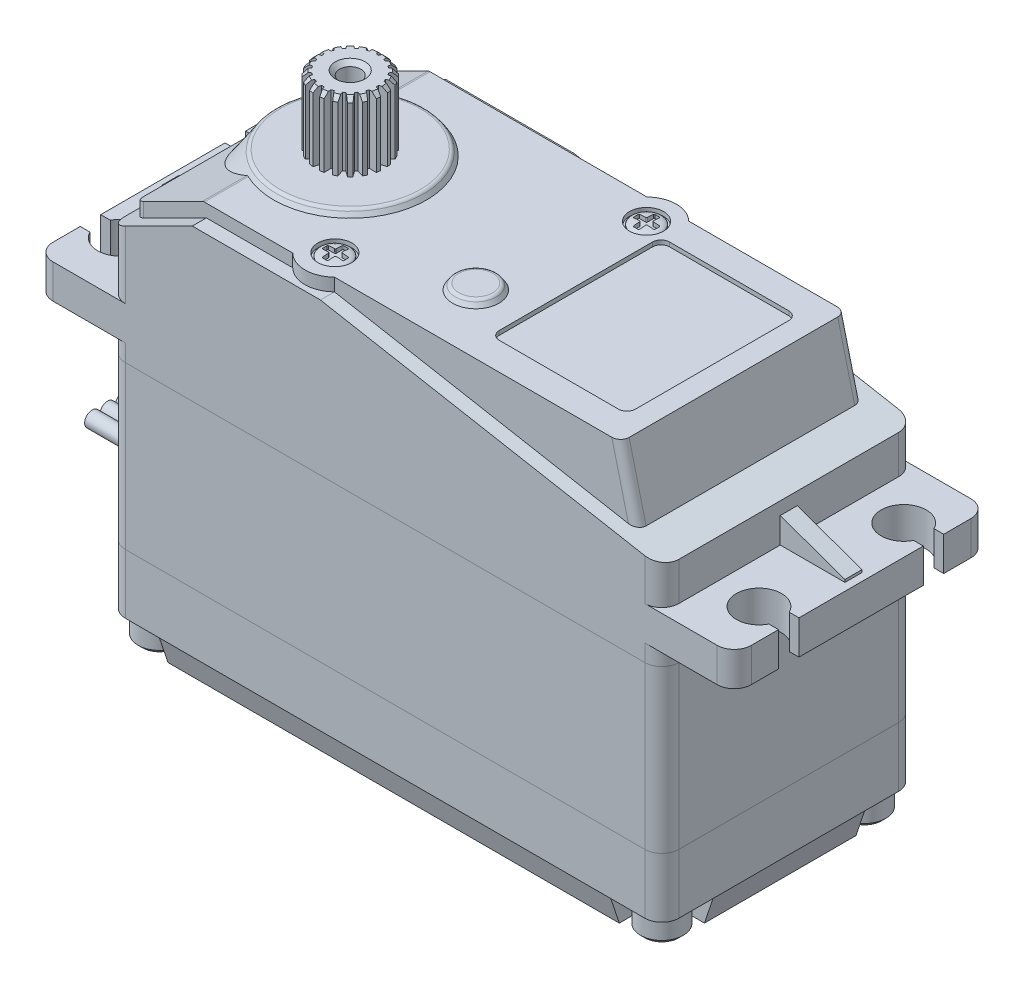
SolidWorks part; units mm, degrees
ref_plane "Front Plane" through (0, 0, 0) normal (0, 0, 1) x (1, 0, 0)
ref_plane "Top Plane" through (0, 0, 0) normal (0, 1, 0) x (1, 0, 0)
ref_plane "Right Plane" through (0, 0, 0) normal (1, 0, 0) x (0, 0, -1)
sketch "Sketch1" plane through (0, 0, 0) normal (0, 1, 0) x (1, 0, 0)
  line L0 (11.399, -13.25) -> (47, -13.25)
  line L1 (-12, 13.25) -> (21.601, 13.25)
  line L2 (-12, 13.25) -> (-12, -13.25)
  line L3 (-12, -13.25) -> (6.5, -13.25)
  line L4 (47, 13.25) -> (47, -13.25)
  line L5 (-12, 13.25) -> (47, -13.25) construction
  line L6 (-12, -13.25) -> (47, 13.25) construction
  line L7 (26.5, 13.25) -> (47, 13.25)
  arc A0 (6.5, -13.25) -> (11.399, -13.25) centre (8.9495, -10.75) ccw
  arc A1 (26.5, 13.25) -> (21.601, 13.25) centre (24.0505, 10.75) ccw
  point P0 (17.5, 0)
  dimension "D4" = 7
  dimension "D1" = 59
  dimension "D2" = 26.5
  dimension "D3" = 47
  dimension "D5" = 2.5
  dimension "D6" = 2.5
  dimension "D7" = 18.5
  dimension "D8" = 20.5
extrude "Boss-Extrude1" add sketch "Sketch1" against normal blind 8
chamfer "Chamfer1" distance 4 distance2 8 1 edges at (-12, 0, 0) first distance on face at (-12, -4, 0)
chamfer "Chamfer2" distance 8 distance2 2 1 edges at (47, 0, 0) first distance on face at (47, -4, 0)
fillet "Fillet1" radius 1 4 edges at (46, -4, -13.25) (46, -4, 13.25) (-12, -6, -13.25) (-12, -6, 13.25)
sketch "Sketch2" plane through (0, 0, 0) normal (0, 1, 0) x (1, 0, 0)
  line L0 (21, -8.5) -> (0, -8.5) construction
  circle A0 centre (0, 0) radius 8.5
  circle A1 centre (21, -6.25) radius 2.25
  dimension "D1" = 17
  dimension "D2" = 4.5
  dimension "D3" = 21
extrude "Boss-Extrude2" add sketch "Sketch2" against normal blind 5 draft 34 from offset 0.7 draft outward yes
fillet "Fillet2" radius 0.5 1 edges at (21, 0.7, 8.5)
sketch "Sketch3" plane through (0, 0, 0) normal (0, 0, 1) x (1, 0, 0)
  line L0 (-3.6459, -1.5) -> (-13.5, -6.4271)
  line L1 (-13.5, -6.4271) -> (-13.5, -13.3216)
  line L2 (-13.5, -13.3216) -> (-22, -13.3216)
  line L3 (-22, -13.3216) -> (-22, -17.3216)
  line L4 (-22, -17.3216) -> (-13.5, -17.3216)
  line L5 (-13.5, -17.3216) -> (-13.5, -19.3216)
  line L6 (-13.5, -19.3216) -> (51.5, -19.3216)
  line L7 (51.5, -19.3216) -> (51.5, -17.3216)
  line L8 (51.5, -17.3216) -> (60, -17.3216)
  line L9 (60, -17.3216) -> (60, -13.3216)
  line L10 (60, -13.3216) -> (51.5, -13.3216)
  line L11 (51.5, -13.3216) -> (51.5, -8.8216)
  line L12 (51.5, -8.8216) -> (11.399, -1.5)
  line L13 (11.399, -8) -> (11.399, 0) construction
  line L14 (11.399, -1.5) -> (-3.6459, -1.5)
  line L15 (-4, 0) -> (-11, -3.5) construction
  line L16 (-4, 0) -> (6.5, 0) construction
  line L17 (-12, -8) -> (-12, -4) construction
  dimension "D1" = 2
  dimension "D2" = 4
  dimension "D3" = 4.5
  dimension "D4" = 1.5
  dimension "D5" = 1.5
  dimension "D6" = 1.5
  dimension "D7" = 65
  dimension "D8" = 8.5
extrude "Boss-Extrude3" add sketch "Sketch3" along normal mid plane 29.8
fillet "Fillet3" radius 2 12 edges at (60, -15.3216, -14.9) (60, -15.3216, 14.9) (-22, -15.3216, 14.9) (-22, -15.3216, -14.9) (51.5, -18.3216, 14.9) (51.5, -18.3216, -14.9) (-13.5, -18.3216, 14.9) (-13.5, -18.3216, -14.9) (-13.5, -9.8743, -14.9) (-13.5, -9.8743, 14.9) (51.5, -11.0716, -14.9) (51.5, -11.0716, 14.9)
sketch "Sketch4" plane through (0, 0, 0) normal (0, 1, 0) x (1, 0, 0)
  line L0 (45, -12.25) -> (45, 12.25) construction
  line L1 (27.5, 10) -> (41.5, 10)
  line L2 (26.5, 9) -> (26.5, -9)
  line L3 (27.5, -10) -> (41.5, -10)
  line L4 (42.5, 9) -> (42.5, -9)
  line L5 (26.5, 10) -> (42.5, -10) construction
  line L6 (26.5, -10) -> (42.5, 10) construction
  circle A0 centre (24.0505, 10.75) radius 2
  circle A1 centre (8.9495, -10.75) radius 2
  arc A2 (41.5, 10) -> (42.5, 9) centre (41.5, 9) cw
  arc A3 (27.5, 10) -> (26.5, 9) centre (27.5, 9) ccw
  arc A4 (26.5, -9) -> (27.5, -10) centre (27.5, -9) ccw
  arc A5 (41.5, -10) -> (42.5, -9) centre (41.5, -9) ccw
  point P0 (34.5, 0)
  dimension "D1" = 4
  dimension "D5" = 1
  dimension "D2" = 20
  dimension "D3" = 16
  dimension "D4" = 2.5
extrude "Cut-Extrude1" cut sketch "Sketch4" against normal blind 0.5
sketch "Sketch5" plane through (0, -13.3216, 0) normal (0, 1, 0) x (1, 0, 0)
  line L0 (-22, 0) -> (60, 0) construction
  line L1 (-22, -12.9) -> (-22, 12.9) construction
  line L2 (60, -12.9) -> (60, 12.9) construction
  line L3 (19, 0) -> (19, 21.0756) construction
  line L4 (58.8627, -7.3) -> (60, -7.3)
  line L5 (58.8627, -9.7) -> (60, -9.7)
  line L6 (60, -9.7) -> (60, -7.3)
  line L7 (60, 9.7) -> (60, 7.3)
  line L8 (58.8627, 9.7) -> (60, 9.7)
  line L9 (58.8627, 7.3) -> (60, 7.3)
  line L10 (-20.8627, 7.3) -> (-22, 7.3)
  line L11 (-20.8627, 9.7) -> (-22, 9.7)
  line L12 (-22, 9.7) -> (-22, 7.3)
  line L13 (-22, -9.7) -> (-22, -7.3)
  line L14 (-20.8627, -9.7) -> (-22, -9.7)
  line L15 (-20.8627, -7.3) -> (-22, -7.3)
  arc A0 (58.8627, -7.3) -> (58.8627, -9.7) centre (56.5, -8.5) ccw
  arc A1 (58.8627, 7.3) -> (58.8627, 9.7) centre (56.5, 8.5) cw
  arc A2 (-20.8627, 7.3) -> (-20.8627, 9.7) centre (-18.5, 8.5) ccw
  arc A3 (-20.8627, -7.3) -> (-20.8627, -9.7) centre (-18.5, -8.5) cw
  dimension "D1" = 17
  dimension "D3" = 5.3
  dimension "D2" = 75
  dimension "D4" = 2.4
extrude "Cut-Extrude2" cut sketch "Sketch5" against normal through all
sketch "Sketch6" plane through (0, -19.3216, 0) normal (0, -1, 0) x (1, 0, 0)
  line L4 (51.5, -12.9) -> (51.5, 12.9)
  line L5 (49.5, 14.9) -> (-11.5, 14.9)
  line L6 (-13.5, 12.9) -> (-13.5, -12.9)
  line L7 (-11.5, -14.9) -> (49.5, -14.9)
  line L8 (51.5, -12.9) -> (51.5, 12.9)
  line L9 (49.5, 14.9) -> (-11.5, 14.9)
  line L10 (-13.5, 12.9) -> (-13.5, -12.9)
  line L11 (-11.5, -14.9) -> (49.5, -14.9)
  arc A4 (51.5, 12.9) -> (49.5, 14.9) centre (49.5, 12.9) ccw
  arc A5 (-11.5, 14.9) -> (-13.5, 12.9) centre (-11.5, 12.9) ccw
  arc A6 (-13.5, -12.9) -> (-11.5, -14.9) centre (-11.5, -12.9) ccw
  arc A7 (49.5, -14.9) -> (51.5, -12.9) centre (49.5, -12.9) ccw
  arc A8 (51.5, 12.9) -> (49.5, 14.9) centre (49.5, 12.9) ccw
  arc A9 (-11.5, 14.9) -> (-13.5, 12.9) centre (-11.5, 12.9) ccw
  arc A10 (-13.5, -12.9) -> (-11.5, -14.9) centre (-11.5, -12.9) ccw
  arc A11 (49.5, -14.9) -> (51.5, -12.9) centre (49.5, -12.9) ccw
  dimension "D1" = 0
extrude "Boss-Extrude4" add sketch "Sketch6" along normal blind 19 separate body
sketch "Sketch7" plane through (0, -38.3216, 0) normal (0, -1, 0) x (1, 0, 0)
  line L4 (51.5, -12.9) -> (51.5, 12.9)
  line L5 (49.5, 14.9) -> (-11.5, 14.9)
  line L6 (-13.5, 12.9) -> (-13.5, -12.9)
  line L7 (-11.5, -14.9) -> (49.5, -14.9)
  line L8 (51.5, -12.9) -> (51.5, 12.9)
  line L9 (49.5, 14.9) -> (-11.5, 14.9)
  line L10 (-13.5, 12.9) -> (-13.5, -12.9)
  line L11 (-11.5, -14.9) -> (49.5, -14.9)
  arc A4 (49.5, -14.9) -> (51.5, -12.9) centre (49.5, -12.9) ccw
  arc A5 (51.5, 12.9) -> (49.5, 14.9) centre (49.5, 12.9) ccw
  arc A6 (-11.5, 14.9) -> (-13.5, 12.9) centre (-11.5, 12.9) ccw
  arc A7 (-13.5, -12.9) -> (-11.5, -14.9) centre (-11.5, -12.9) ccw
  arc A8 (49.5, -14.9) -> (51.5, -12.9) centre (49.5, -12.9) ccw
  arc A9 (51.5, 12.9) -> (49.5, 14.9) centre (49.5, 12.9) ccw
  arc A10 (-11.5, 14.9) -> (-13.5, 12.9) centre (-11.5, 12.9) ccw
  arc A11 (-13.5, -12.9) -> (-11.5, -14.9) centre (-11.5, -12.9) ccw
  dimension "D1" = 0
extrude "Boss-Extrude5" add sketch "Sketch7" along normal blind 10 separate body
sketch "Sketch11" plane through (0, 0, 0) normal (0, 0, 1) x (1, 0, 0)
  line L0 (51.5, -10.3216) -> (59.1, -13.0216)
  line L2 (51.5, -13.3216) -> (51.5, -8.8216) construction
  line L3 (58, -13.3216) -> (49.5, -13.3216) construction
  line L5 (19, -19.3216) -> (19, 14.0066) construction
  line L6 (-11.5, -19.3216) -> (49.5, -19.3216) construction
  line L7 (-21.1, -13.0216) -> (-21.1, -13.3216)
  line L8 (59.1, -13.3216) -> (51.5, -13.3216)
  line L9 (51.5, -13.3216) -> (51.5, -10.3216)
  line L10 (51.5, -10.3216) -> (51.5171, -10.3436)
  line L11 (-13.5, -10.3216) -> (-13.5171, -10.3436)
  line L12 (-13.5, -13.3216) -> (-13.5, -10.3216)
  line L13 (-21.1, -13.3216) -> (-13.5, -13.3216)
  line L14 (59.1, -13.0216) -> (59.1, -13.3216)
  line L15 (-13.5, -10.3216) -> (-21.1, -13.0216)
  dimension "D1" = 7.6
  dimension "D2" = 3
  dimension "D3" = 0.3
extrude "Boss-Extrude6" add sketch "Sketch11" along normal mid plane 2 contours L9 L8 L0 | L15 L7 L13 L12 region at (54.2636, -12.3125, 0) region at (-16.2636, -12.3125, 0)
sketch "Sketch12" plane through (0, -48.3216, 0) normal (0, -1, 0) x (1, 0, 0)
  line L0 (65.179, 0) -> (19, 0) construction
  line L1 (49.5, 14.9) -> (-11.5, 14.9) construction
  line L2 (19, 0) -> (19, 14.9) construction
  line L4 (45.5, 14.9) -> (45.5, 8.9)
  line L6 (45.5, 8.9) -> (51.5, 8.9)
  line L9 (45.5, 14.9) -> (49.5, 14.9)
  line L10 (51.5, 12.9) -> (51.5, 8.9)
  line L11 (47.25, -11.1783) -> (48.5, -10.4566)
  line L12 (48.5, 10.4566) -> (49.75, 11.1783)
  line L13 (49.75, 11.1783) -> (49.75, 12.6217)
  line L14 (49.75, 12.6217) -> (48.5, 13.3434)
  line L15 (48.5, 13.3434) -> (47.25, 12.6217)
  line L16 (47.25, 12.6217) -> (47.25, 11.1783)
  line L17 (47.25, 11.1783) -> (48.5, 10.4566)
  line L18 (47.25, -12.6217) -> (47.25, -11.1783)
  line L19 (48.5, -13.3434) -> (47.25, -12.6217)
  line L20 (49.75, -12.6217) -> (48.5, -13.3434)
  line L21 (49.75, -11.1783) -> (49.75, -12.6217)
  line L22 (48.5, -10.4566) -> (49.75, -11.1783)
  line L23 (51.5, -12.9) -> (51.5, -8.9)
  line L24 (45.5, -14.9) -> (49.5, -14.9)
  line L25 (45.5, -8.9) -> (51.5, -8.9)
  line L26 (45.5, -14.9) -> (45.5, -8.9)
  line L27 (-7.5, -14.9) -> (-7.5, -8.9)
  line L28 (-7.5, -8.9) -> (-13.5, -8.9)
  line L29 (-7.5, -14.9) -> (-11.5, -14.9)
  line L30 (-13.5, -12.9) -> (-13.5, -8.9)
  line L31 (-10.5, -10.4566) -> (-11.75, -11.1783)
  line L32 (-11.75, -11.1783) -> (-11.75, -12.6217)
  line L33 (-11.75, -12.6217) -> (-10.5, -13.3434)
  line L34 (-10.5, -13.3434) -> (-9.25, -12.6217)
  line L35 (-9.25, -12.6217) -> (-9.25, -11.1783)
  line L36 (-9.25, 11.1783) -> (-10.5, 10.4566)
  line L37 (-9.25, 12.6217) -> (-9.25, 11.1783)
  line L38 (-10.5, 13.3434) -> (-9.25, 12.6217)
  line L39 (-11.75, 12.6217) -> (-10.5, 13.3434)
  line L40 (-11.75, 11.1783) -> (-11.75, 12.6217)
  line L41 (-10.5, 10.4566) -> (-11.75, 11.1783)
  line L42 (-9.25, -11.1783) -> (-10.5, -10.4566)
  line L43 (-13.5, 12.9) -> (-13.5, 8.9)
  line L44 (-7.5, 14.9) -> (-11.5, 14.9)
  line L45 (-7.5, 8.9) -> (-13.5, 8.9)
  line L46 (-7.5, 14.9) -> (-7.5, 8.9)
  line L47 (49.5, 14.9) -> (-11.5, 14.9) construction
  line L48 (51.5, -12.9) -> (51.5, 12.9) construction
  arc A0 (51.5, 12.9) -> (49.5, 14.9) centre (49.5, 12.9) ccw construction
  arc A1 (51.5, 12.9) -> (49.5, 14.9) centre (49.5, 12.9) ccw
  circle A2 centre (48.5, 11.9) radius 2.5
  circle A3 centre (48.5, 11.9) radius 1.25 construction
  circle A4 centre (48.5, -11.9) radius 1.25 construction
  circle A5 centre (48.5, -11.9) radius 2.5
  arc A6 (51.5, -12.9) -> (49.5, -14.9) centre (49.5, -12.9) cw
  circle A7 centre (-10.5, -11.9) radius 1.25 construction
  circle A8 centre (-10.5, 11.9) radius 1.25 construction
  arc A9 (-13.5, -12.9) -> (-11.5, -14.9) centre (-11.5, -12.9) ccw
  circle A10 centre (-10.5, -11.9) radius 2.5
  circle A11 centre (-10.5, 11.9) radius 2.5
  arc A12 (-13.5, 12.9) -> (-11.5, 14.9) centre (-11.5, 12.9) cw
  point P21 (48.5, 8.9)
  point P23 (45.5, 11.9)
  dimension "D2" = 5
  dimension "D3" = 2.5
  dimension "D1" = 6
extrude "Cut-Extrude3" cut sketch "Sketch12" against normal blind 3 contours A11 L45 L46 | A12 L43 L45 A11 L46 L44 | L41 L36 L37 L38 L39 L40 | A10 L28 L30 A9 L29 L27 | A10 L27 L28 | L35 L42 L31 L32 L33 L34 | A6 L23 L25 A5 L26 L24 | A5 L25 L26 | L22 L11 L18 L19 L20 L21 | L16 L17 L12 L13 L14 L15 | A2 L4 L6 | A2 L6 L10 A1 L9 L4 region at (47.5, -48.3216, 14.8151) region at (48.5, -48.3216, -11.9) region at (48.5, -48.3216, 11.9) region at (50.8542, -48.3216, -14.2542) region at (-9.5, -48.3216, -14.8151) region at (-10.5, -48.3216, -11.9) region at (-10.5, -48.3216, 11.9) region at (-12.8542, -48.3216, 14.2542)
chamfer "Chamfer4" distance 3 distance2 1 4 edges at (51.5, -48.3216, 0) (19, -48.3216, -14.9) (-13.5, -48.3216, 0) (19, -48.3216, 14.9) first distance on face at (51.5, -44.3216, 0) first distance on face at (19, -44.3216, -14.9) first distance on face at (-13.5, -44.3216, 0) first distance on face at (19, -44.3216, 14.9)
chamfer "Chamfer5" distance 0.5 angle 45 4 edges at (-10.5, -48.3216, -14.4) (-10.5, -48.3216, 9.4) (48.5, -48.3216, 9.4) (48.5, -48.3216, -14.4)
sketch "Sketch13" plane through (0, 0.7, 0) normal (0, 1, 0) x (1, 0, 0)
  circle A0 centre (0, 0) radius 4
  circle A1 centre (0, 0) radius 1.25
  dimension "D1" = 8
  dimension "D2" = 2.5
extrude "Boss-Extrude7" add sketch "Sketch13" along normal blind 8 separate body
chamfer "Chamfer6" distance 0.5 angle 45 2 edges at (0, 8.7, 4) (0, 8.7, 1.25)
sketch "Sketch14" plane through (0, 8.7, 0) normal (0, 1, 0) x (1, 0, 0)
  line L0 (3.9799, 0.4) -> (3.2, 0.15)
  line L1 (3.2, 0.15) -> (3.2, -0.15)
  line L2 (3.2, -0.15) -> (3.9799, -0.4)
  line L3 (3.2, 0) -> (0, 0) construction
  line L4 (3.9088, -0.8494) -> (3.0897, -0.8462)
  line L5 (3.0897, -0.8462) -> (2.997, -1.1315)
  line L6 (2.997, -1.1315) -> (3.6616, -1.6103)
  line L7 (3.455, -2.0157) -> (2.677, -1.7596)
  line L8 (2.677, -1.7596) -> (2.5007, -2.0023)
  line L9 (2.5007, -2.0023) -> (2.9847, -2.663)
  line L10 (2.663, -2.9847) -> (2.0023, -2.5007)
  line L11 (2.0023, -2.5007) -> (1.7596, -2.677)
  line L12 (1.7596, -2.677) -> (2.0157, -3.455)
  line L13 (1.6103, -3.6616) -> (1.1315, -2.997)
  line L14 (1.1315, -2.997) -> (0.8462, -3.0897)
  line L15 (0.8462, -3.0897) -> (0.8494, -3.9088)
  line L16 (0.4, -3.9799) -> (0.15, -3.2)
  line L17 (0.15, -3.2) -> (-0.15, -3.2)
  line L18 (-0.15, -3.2) -> (-0.4, -3.9799)
  line L19 (-0.8494, -3.9088) -> (-0.8462, -3.0897)
  line L20 (-0.8462, -3.0897) -> (-1.1315, -2.997)
  line L21 (-1.1315, -2.997) -> (-1.6103, -3.6616)
  line L22 (-2.0157, -3.455) -> (-1.7596, -2.677)
  line L23 (-1.7596, -2.677) -> (-2.0023, -2.5007)
  line L24 (-2.0023, -2.5007) -> (-2.663, -2.9847)
  line L25 (-2.9847, -2.663) -> (-2.5007, -2.0023)
  line L26 (-2.5007, -2.0023) -> (-2.677, -1.7596)
  line L27 (-2.677, -1.7596) -> (-3.455, -2.0157)
  line L28 (-3.6616, -1.6103) -> (-2.997, -1.1315)
  line L29 (-2.997, -1.1315) -> (-3.0897, -0.8462)
  line L30 (-3.0897, -0.8462) -> (-3.9088, -0.8494)
  line L31 (-3.9799, -0.4) -> (-3.2, -0.15)
  line L32 (-3.2, -0.15) -> (-3.2, 0.15)
  line L33 (-3.2, 0.15) -> (-3.9799, 0.4)
  line L34 (-3.9088, 0.8494) -> (-3.0897, 0.8462)
  line L35 (-3.0897, 0.8462) -> (-2.997, 1.1315)
  line L36 (-2.997, 1.1315) -> (-3.6616, 1.6103)
  line L37 (-3.455, 2.0157) -> (-2.677, 1.7596)
  line L38 (-2.677, 1.7596) -> (-2.5007, 2.0023)
  line L39 (-2.5007, 2.0023) -> (-2.9847, 2.663)
  line L40 (-2.663, 2.9847) -> (-2.0023, 2.5007)
  line L41 (-2.0023, 2.5007) -> (-1.7596, 2.677)
  line L42 (-1.7596, 2.677) -> (-2.0157, 3.455)
  line L43 (-1.6103, 3.6616) -> (-1.1315, 2.997)
  line L44 (-1.1315, 2.997) -> (-0.8462, 3.0897)
  line L45 (-0.8462, 3.0897) -> (-0.8494, 3.9088)
  line L46 (-0.4, 3.9799) -> (-0.15, 3.2)
  line L47 (-0.15, 3.2) -> (0.15, 3.2)
  line L48 (0.15, 3.2) -> (0.4, 3.9799)
  line L49 (0.8494, 3.9088) -> (0.8462, 3.0897)
  line L50 (0.8462, 3.0897) -> (1.1315, 2.997)
  line L51 (1.1315, 2.997) -> (1.6103, 3.6616)
  line L52 (2.0157, 3.455) -> (1.7596, 2.677)
  line L53 (1.7596, 2.677) -> (2.0023, 2.5007)
  line L54 (2.0023, 2.5007) -> (2.663, 2.9847)
  line L55 (2.9847, 2.663) -> (2.5007, 2.0023)
  line L56 (2.5007, 2.0023) -> (2.677, 1.7596)
  line L57 (2.677, 1.7596) -> (3.455, 2.0157)
  line L58 (3.6616, 1.6103) -> (2.997, 1.1315)
  line L59 (2.997, 1.1315) -> (3.0897, 0.8462)
  line L60 (3.0897, 0.8462) -> (3.9088, 0.8494)
  circle A0 centre (0, 0) radius 4 construction
  arc A1 (3.9799, -0.4) -> (3.9799, 0.4) centre (0, 0) ccw
  arc A2 (3.6616, -1.6103) -> (3.9088, -0.8494) centre (0, 0) ccw
  arc A3 (2.9847, -2.663) -> (3.455, -2.0157) centre (0, 0) ccw
  arc A4 (2.0157, -3.455) -> (2.663, -2.9847) centre (0, 0) ccw
  arc A5 (0.8494, -3.9088) -> (1.6103, -3.6616) centre (0, 0) ccw
  arc A6 (-0.4, -3.9799) -> (0.4, -3.9799) centre (0, 0) ccw
  arc A7 (-1.6103, -3.6616) -> (-0.8494, -3.9088) centre (0, 0) ccw
  arc A8 (-2.663, -2.9847) -> (-2.0157, -3.455) centre (0, 0) ccw
  arc A9 (-3.455, -2.0157) -> (-2.9847, -2.663) centre (0, 0) ccw
  arc A10 (-3.9088, -0.8494) -> (-3.6616, -1.6103) centre (0, 0) ccw
  arc A11 (-3.9799, 0.4) -> (-3.9799, -0.4) centre (0, 0) ccw
  arc A12 (-3.6616, 1.6103) -> (-3.9088, 0.8494) centre (0, 0) ccw
  arc A13 (-2.9847, 2.663) -> (-3.455, 2.0157) centre (0, 0) ccw
  arc A14 (-2.0157, 3.455) -> (-2.663, 2.9847) centre (0, 0) ccw
  arc A15 (-0.8494, 3.9088) -> (-1.6103, 3.6616) centre (0, 0) ccw
  arc A16 (0.4, 3.9799) -> (-0.4, 3.9799) centre (0, 0) ccw
  arc A17 (1.6103, 3.6616) -> (0.8494, 3.9088) centre (0, 0) ccw
  arc A18 (2.663, 2.9847) -> (2.0157, 3.455) centre (0, 0) ccw
  arc A19 (3.455, 2.0157) -> (2.9847, 2.663) centre (0, 0) ccw
  arc A20 (3.9088, 0.8494) -> (3.6616, 1.6103) centre (0, 0) ccw
  point P85 (0, 0)
  dimension "D1" = 0.3
  dimension "D2" = 0.8
  dimension "D3" = 3.2
  dimension "D4" = 20
extrude "Cut-Extrude4" cut sketch "Sketch14" against normal through all
sketch "Sketch15" plane through (0, -0.5, 0) normal (0, 1, 0) x (1, 0, 0)
  circle A0 centre (8.9495, -10.75) radius 1.75
  circle A1 centre (8.9495, -10.75) radius 2 construction
  circle A2 centre (24.0505, 10.75) radius 2 construction
  circle A5 centre (24.0505, 10.75) radius 1.75
  dimension "D1" = 3.5
extrude "Boss-Extrude8" add sketch "Sketch15" along normal blind 0.5 separate body
fillet "Fillet4" radius 0.32 1 edges at (8.9495, 0, 12.5) second distance 1.2 first distance on face at (8.9495, 0, 12.5)
fillet "Fillet5" radius 0.32 1 edges at (24.0505, 0, -9) second distance 1.2 first distance on face at (24.0505, 0, -9)
sketch "Sketch16" plane through (0, 0, 0) normal (0, 1, 0) x (1, 0, 0)
  line L0 (8.607, -9.4483) -> (9.307, -9.4483)
  line L1 (23.7005, 12) -> (24.4005, 12)
  line L2 (23.7005, 12) -> (23.7005, 9.5)
  line L3 (23.7005, 9.5) -> (24.4005, 9.5)
  line L4 (24.4005, 12) -> (24.4005, 9.5)
  line L5 (23.7005, 12) -> (24.4005, 9.5) construction
  line L6 (23.7005, 9.5) -> (24.4005, 12) construction
  line L7 (22.8005, 11.1) -> (25.3005, 11.1)
  line L8 (22.8005, 11.1) -> (22.8005, 10.4)
  line L9 (22.8005, 10.4) -> (25.3005, 10.4)
  line L10 (25.3005, 11.1) -> (25.3005, 10.4)
  line L11 (22.8005, 11.1) -> (25.3005, 10.4) construction
  line L12 (22.8005, 10.4) -> (25.3005, 11.1) construction
  line L13 (8.607, -9.4483) -> (8.607, -11.9483)
  line L14 (8.607, -11.9483) -> (9.307, -11.9483)
  line L15 (9.307, -9.4483) -> (9.307, -11.9483)
  line L16 (8.607, -9.4483) -> (9.307, -11.9483) construction
  line L17 (8.607, -11.9483) -> (9.307, -9.4483) construction
  line L18 (7.707, -10.3483) -> (10.207, -10.3483)
  line L19 (7.707, -10.3483) -> (7.707, -11.0483)
  line L20 (7.707, -11.0483) -> (10.207, -11.0483)
  line L21 (10.207, -10.3483) -> (10.207, -11.0483)
  line L22 (7.707, -10.3483) -> (10.207, -11.0483) construction
  line L23 (7.707, -11.0483) -> (10.207, -10.3483) construction
  point P0 (24.0505, 10.75)
  point P5 (24.0505, 10.75)
  point P11 (8.957, -10.6983)
  point P16 (8.957, -10.6983)
  dimension "D1" = 2.5
  dimension "D2" = 0.7
  dimension "D3" = 2.5
  dimension "D4" = 0.7
extrude "Cut-Extrude5" cut sketch "Sketch16" against normal blind 0.48 contours L15 L14 L13 L0 | L20 L21 L18 L19 | L9 L10 L7 L8 | L4 L3 L2 L1
fillet "Fillet6" radius 0.1 12 edges at (24.4005, -0.24, -10.4) (24.4005, -0.24, -11.1) (23.7005, -0.24, -10.4) (23.7005, -0.24, -11.1) (23.7005, -0.2749, -12) (24.4005, -0.2749, -12) (25.3005, -0.2749, -11.1) (25.3005, -0.2749, -10.4) (24.4005, -0.2749, -9.5) (23.7005, -0.2749, -9.5) (22.8005, -0.2749, -10.4) (22.8005, -0.2749, -11.1)
fillet "Fillet7" radius 0.1 12 edges at (10.207, -0.2773, 10.3483) (9.307, -0.2701, 11.9483) (10.207, -0.2743, 11.0483) (7.707, -0.2728, 11.0483) (8.607, -0.2697, 11.9483) (9.307, -0.24, 11.0483) (8.607, -0.24, 11.0483) (7.707, -0.2757, 10.3483) (8.607, -0.2803, 9.4483) (8.607, -0.24, 10.3483) (9.307, -0.24, 10.3483) (9.307, -0.2807, 9.4483)
fillet "Fillet8" radius 0.5 3 edges at (0, 0.7, 8.5) (-4, 0, -10.6406) (-4, 0, 10.6406)
sketch "Sketch17" plane through (-13.5, 0, 0) normal (-1, 0, 0) x (0, 0, 1)
  line L0 (12.9, -38.3216) -> (-12.9, -38.3216) construction
  line L1 (3.4, -38.3216) -> (-3.4, -38.3216)
  line L2 (3.4, -38.3216) -> (3.4, -41.8216)
  line L3 (3.4, -41.8216) -> (-3.4, -41.8216)
  line L4 (-3.4, -38.3216) -> (-3.4, -41.8216)
  line L5 (0, -38.3216) -> (0, 0) construction
  dimension "D1" = 6.8
  dimension "D2" = 3.5
extrude "Boss-Extrude9" add sketch "Sketch17" along normal blind 1 separate body
sketch "Sketch18" plane through (-14.5, 0, 0) normal (-1, 0, 0) x (0, 0, 1)
  line L4 (3.4, -41.8216) -> (3.4, -38.3216)
  line L5 (3.4, -38.3216) -> (-3.4, -38.3216)
  line L6 (-3.4, -38.3216) -> (-3.4, -41.8216)
  line L7 (-3.4, -41.8216) -> (3.4, -41.8216)
  line L8 (3.4, -41.8216) -> (3.4, -38.3216)
  line L9 (3.4, -38.3216) -> (-3.4, -38.3216)
  line L10 (-3.4, -38.3216) -> (-3.4, -41.8216)
  line L11 (-3.4, -41.8216) -> (3.4, -41.8216)
  dimension "D1" = 0
extrude "Boss-Extrude10" add sketch "Sketch18" along normal blind 4 draft 10
sketch "Sketch19" plane through (-18.5, 0, 0) normal (-1, 0, 0) x (0, 0, 1)
  line L0 (0, -40.0716) -> (0, -39.0269) construction
  line L1 (2.6947, -39.0269) -> (-2.6947, -39.0269) construction
  line L2 (0, -40.0716) -> (0, -41.1163) construction
  line L3 (-2.6947, -41.1163) -> (2.6947, -41.1163) construction
  circle A0 centre (0, -40.0716) radius 0.89
  circle A1 centre (1.8, -40.0716) radius 0.89
  circle A2 centre (-1.8, -40.0716) radius 0.89
  dimension "D1" = 1.78
  dimension "D2" = 1.8
extrude "Boss-Extrude12" add sketch "Sketch19" along normal blind 10
